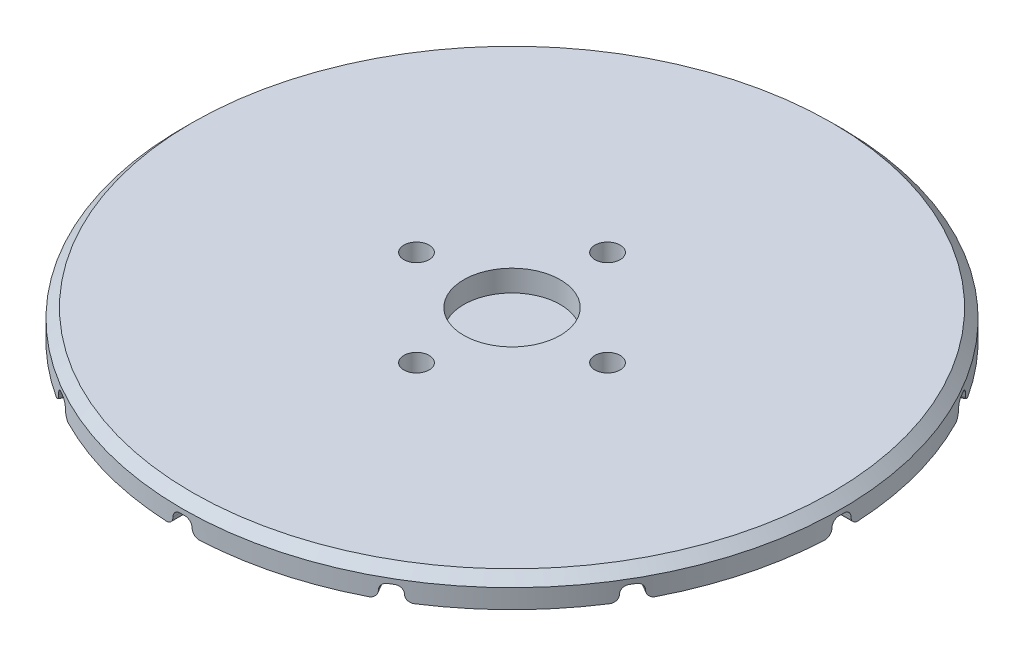
SolidWorks part; units mm, degrees
ref_plane "Ebene vorne" through (0, 0, 0) normal (0, 0, 1) x (1, 0, 0)
ref_plane "Ebene oben" through (0, 0, 0) normal (0, 1, 0) x (1, 0, 0)
ref_plane "Ebene rechts" through (0, 0, 0) normal (1, 0, 0) x (0, 0, -1)
sketch "Skizze1" plane through (0, 0, 0) normal (0, 1, 0) x (1, 0, 0)
  circle A0 centre (0, 0) radius 69
  dimension "D1" = 138
extrude "Aufsatz-Linear austragen1" add sketch "Skizze1" along normal blind 3
sketch "Skizze2" plane through (0, 0, 0) normal (0, -1, 0) x (1, 0, 0)
  circle A0 centre (0, 0) radius 25
  dimension "D1" = 50
extrude "Aufsatz-Linear austragen2" add sketch "Skizze2" along normal blind 32.8
chamfer "Fase1" distance 2 angle 45 1 edges at (0, 3, 69)
chamfer "Fase2" distance 0.4 angle 45 1 edges at (0, -32.8, -25)
sketch "Skizze3" plane through (0, 3, 0) normal (0, 1, 0) x (1, 0, 0)
  circle A0 centre (0, 0) radius 10.1
  dimension "D1" = 20.2
extrude "Schnitt-Linear austragen1" cut sketch "Skizze3" against normal blind 4.5
sketch "Skizze4" plane through (0, 3, 0) normal (0, 1, 0) x (1, 0, 0)
  circle A0 centre (0, 0) radius 20 construction
  circle A1 centre (-20, 0) radius 2.65
  circle A2 centre (0, 20) radius 2.65
  circle A3 centre (20, 0) radius 2.65
  circle A4 centre (0, -20) radius 2.65
  dimension "D1" = 40
  dimension "D2" = 5.3
extrude "Schnitt-Linear austragen2" cut sketch "Skizze4" against normal blind 20
sketch "Skizze5" plane through (0, -32.8, 0) normal (0, -1, 0) x (1, 0, 0)
  circle A0 centre (0, 0) radius 24
  dimension "D1" = 48
extrude "Schnitt-Linear austragen3" cut sketch "Skizze5" against normal blind 1
sketch "Skizze6" plane through (0, 0, 0) normal (0, -1, 0) x (1, 0, 0)
  circle A0 centre (0, 0) radius 69
  circle A1 centre (0, 0) radius 59
  circle A2 centre (0, 0) radius 69 construction
  dimension "D1" = 10
extrude "Aufsatz-Linear austragen3" add sketch "Skizze6" along normal blind 3
sketch "Skizze7" plane through (0, -3, 0) normal (0, -1, 0) x (1, 0, 0)
  line L0 (0, 0) -> (69, 0) construction
  line L1 (58.9661, 2) -> (68.971, 2)
  line L2 (58.9661, -2) -> (68.971, -2)
  line L3 (50.0661, -31.2151) -> (58.7306, -36.2176)
  line L4 (52.0661, -27.751) -> (60.7306, -32.7535)
  line L5 (27.751, -52.0661) -> (32.7535, -60.7306)
  line L6 (31.2151, -50.0661) -> (36.2176, -58.7306)
  line L7 (-2, -58.9661) -> (-2, -68.971)
  line L8 (2, -58.9661) -> (2, -68.971)
  line L9 (-31.2151, -50.0661) -> (-36.2176, -58.7306)
  line L10 (-27.751, -52.0661) -> (-32.7535, -60.7306)
  line L11 (-52.0661, -27.751) -> (-60.7306, -32.7535)
  line L12 (-50.0661, -31.2151) -> (-58.7306, -36.2176)
  line L13 (-58.9661, 2) -> (-68.971, 2)
  line L14 (-58.9661, -2) -> (-68.971, -2)
  line L15 (-50.0661, 31.2151) -> (-58.7306, 36.2176)
  line L16 (-52.0661, 27.751) -> (-60.7306, 32.7535)
  line L17 (-27.751, 52.0661) -> (-32.7535, 60.7306)
  line L18 (-31.2151, 50.0661) -> (-36.2176, 58.7306)
  line L19 (2, 58.9661) -> (2, 68.971)
  line L20 (-2, 58.9661) -> (-2, 68.971)
  line L21 (31.2151, 50.0661) -> (36.2176, 58.7306)
  line L22 (27.751, 52.0661) -> (32.7535, 60.7306)
  line L23 (52.0661, 27.751) -> (60.7306, 32.7535)
  line L24 (50.0661, 31.2151) -> (58.7306, 36.2176)
  circle A0 centre (0, 0) radius 69 construction
  arc A1 (58.9661, -2) -> (58.9661, 2) centre (0, 0) ccw
  arc A2 (68.971, -2) -> (68.971, 2) centre (0, 0) ccw
  circle A3 centre (0, 0) radius 59 construction
  arc A4 (50.0661, -31.2151) -> (52.0661, -27.751) centre (0, 0) ccw
  arc A5 (58.7306, -36.2176) -> (60.7306, -32.7535) centre (0, 0) ccw
  arc A6 (27.751, -52.0661) -> (31.2151, -50.0661) centre (0, 0) ccw
  arc A7 (32.7535, -60.7306) -> (36.2176, -58.7306) centre (0, 0) ccw
  arc A8 (-2, -58.9661) -> (2, -58.9661) centre (0, 0) ccw
  arc A9 (-2, -68.971) -> (2, -68.971) centre (0, 0) ccw
  arc A10 (-31.2151, -50.0661) -> (-27.751, -52.0661) centre (0, 0) ccw
  arc A11 (-36.2176, -58.7306) -> (-32.7535, -60.7306) centre (0, 0) ccw
  arc A12 (-52.0661, -27.751) -> (-50.0661, -31.2151) centre (0, 0) ccw
  arc A13 (-60.7306, -32.7535) -> (-58.7306, -36.2176) centre (0, 0) ccw
  arc A14 (-58.9661, 2) -> (-58.9661, -2) centre (0, 0) ccw
  arc A15 (-68.971, 2) -> (-68.971, -2) centre (0, 0) ccw
  arc A16 (-50.0661, 31.2151) -> (-52.0661, 27.751) centre (0, 0) ccw
  arc A17 (-58.7306, 36.2176) -> (-60.7306, 32.7535) centre (0, 0) ccw
  arc A18 (-27.751, 52.0661) -> (-31.2151, 50.0661) centre (0, 0) ccw
  arc A19 (-32.7535, 60.7306) -> (-36.2176, 58.7306) centre (0, 0) ccw
  arc A20 (2, 58.9661) -> (-2, 58.9661) centre (0, 0) ccw
  arc A21 (2, 68.971) -> (-2, 68.971) centre (0, 0) ccw
  arc A22 (31.2151, 50.0661) -> (27.751, 52.0661) centre (0, 0) ccw
  arc A23 (36.2176, 58.7306) -> (32.7535, 60.7306) centre (0, 0) ccw
  arc A24 (52.0661, 27.751) -> (50.0661, 31.2151) centre (0, 0) ccw
  arc A25 (60.7306, 32.7535) -> (58.7306, 36.2176) centre (0, 0) ccw
  point P59 (0, 0)
  dimension "D1" = 4
  dimension "D2" = 2
extrude "Schnitt-Linear austragen4" cut sketch "Skizze7" against normal blind 3
fillet "Verrundung1" radius 1.5 48 edges at (33.7163, 0, 54.3984) (30.2522, 0, 56.3984) (33.7163, -3, 54.3984) (30.2522, -3, 56.3984) (54.3984, 0, 33.7163) (54.3984, -3, 33.7163) (56.3984, -3, 30.2522) (56.3984, 0, 30.2522) (63.9686, 0, -2) (63.9686, 0, 2) (63.9686, -3, 2) (63.9686, -3, -2) (56.3984, 0, -30.2522) (54.3984, 0, -33.7163) (56.3984, -3, -30.2522) (54.3984, -3, -33.7163) (33.7163, -3, -54.3984) (30.2522, 0, -56.3984) (30.2522, -3, -56.3984) (33.7163, 0, -54.3984) (2, 0, -63.9686) (-2, 0, -63.9686) (-2, -3, -63.9686) (2, -3, -63.9686) (-33.7163, 0, -54.3984) (-30.2522, -3, -56.3984) (-30.2522, 0, -56.3984) (-33.7163, -3, -54.3984) (-54.3984, -3, -33.7163) (-56.3984, 0, -30.2522) (-54.3984, 0, -33.7163) (-56.3984, -3, -30.2522) (-63.9686, -3, 2) (-63.9686, 0, 2) (-63.9686, 0, -2) (-63.9686, -3, -2) (-54.3984, -3, 33.7163) (-54.3984, 0, 33.7163) (-56.3984, 0, 30.2522) (-56.3984, -3, 30.2522) (-33.7163, 0, 54.3984) (-30.2522, 0, 56.3984) (-33.7163, -3, 54.3984) (-30.2522, -3, 56.3984) (-2, -3, 63.9686) (-2, 0, 63.9686) (2, 0, 63.9686) (2, -3, 63.9686)
